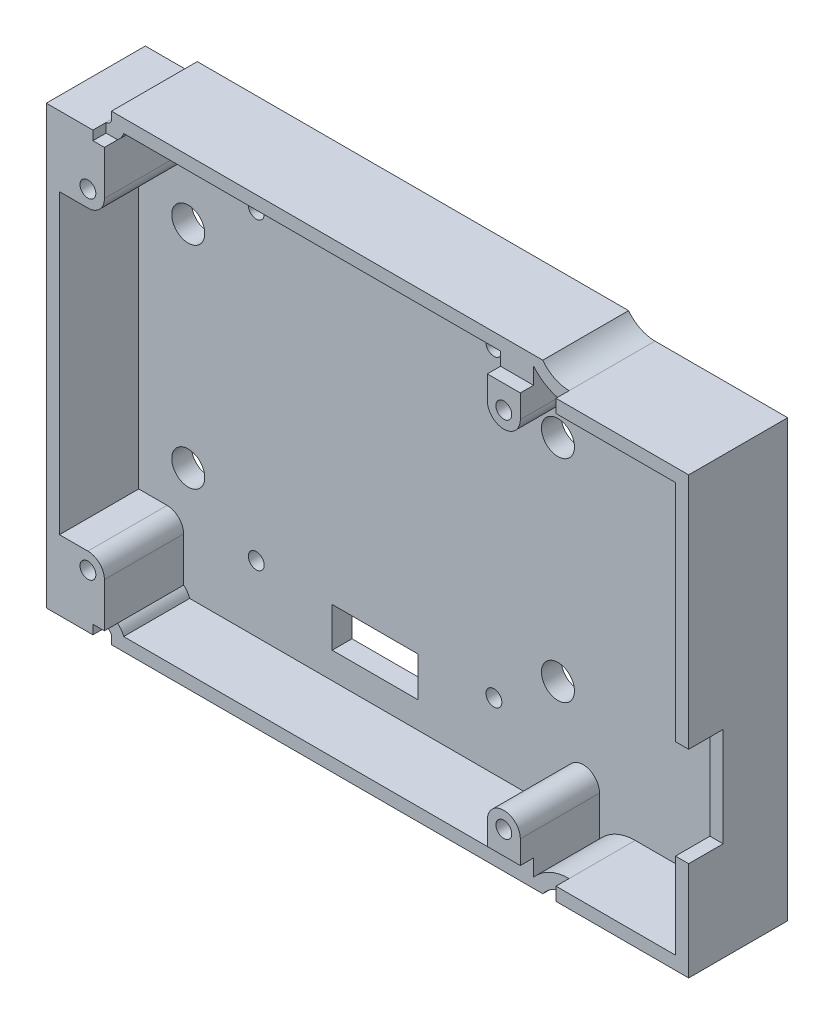
SolidWorks part; units mm, degrees
ref_plane "Ebene vorne" through (0, 0, 0) normal (0, 0, 1) x (1, 0, 0)
ref_plane "Ebene oben" through (0, 0, 0) normal (0, 1, 0) x (1, 0, 0)
ref_plane "Ebene rechts" through (0, 0, 0) normal (1, 0, 0) x (0, 0, -1)
sketch "Skizze1" plane through (0, 0, 0) normal (0, 0, 1) x (1, 0, 0)
  line L0 (-40.78, 38.7) -> (-40.78, 33.92)
  line L1 (-41.59, 33.11) -> (-48.65, 33.11)
  line L2 (-48.65, 33.11) -> (-48.65, -33.11)
  line L3 (-48.65, -33.11) -> (-41.59, -33.11)
  line L4 (-40.78, -33.92) -> (-40.78, -38.7)
  line L5 (-40.78, -38.7) -> (-39.35, -38.7)
  line L6 (-39.35, -38.7) -> (-39.35, 38.7)
  line L7 (-39.35, 38.7) -> (-40.78, 38.7)
  line L8 (48.65, 3) -> (45.65, 3)
  line L9 (45.65, 3) -> (45.65, -30)
  line L10 (45.65, -30) -> (34.2, -30)
  line L11 (34.2, -33) -> (48.65, -33)
  line L12 (48.65, -33) -> (48.65, 3)
  line L13 (45.65, 18) -> (48.65, 18)
  line L14 (48.65, 18) -> (48.65, 33)
  line L15 (48.65, 33) -> (34.2, 33)
  line L16 (34.2, 30) -> (45.65, 30)
  line L17 (45.65, 30) -> (45.65, 18)
  line L18 (34.2, 33) -> (28.5521, 33)
  line L19 (23.85, 36.3) -> (5.65, 36.3)
  line L20 (2.287, 35) -> (-20.522, 35)
  line L21 (-25.35, 38.7) -> (-27.35, 38.7)
  line L22 (-27.35, 38.7) -> (-27.35, -38.7)
  line L23 (-27.35, -38.7) -> (-25.35, -38.7)
  line L24 (-20.522, -35) -> (2.287, -35)
  line L25 (5.65, -36.3) -> (23.85, -36.3)
  line L26 (28.5521, -33) -> (34.2, -33)
  line L27 (34.2, -30) -> (23.85, -30)
  line L28 (23.85, -30) -> (23.85, -24)
  line L29 (23.85, -24) -> (17.45, -24)
  line L30 (17.45, -24) -> (17.45, -33.3)
  line L31 (17.45, -33.3) -> (9.3559, -33.3)
  line L32 (7.65, -33) -> (-24.35, -33)
  line L33 (-24.35, -33) -> (-24.35, 33)
  line L34 (-24.35, 33) -> (7.65, 33)
  line L35 (9.3559, 33.3) -> (17.45, 33.3)
  line L36 (17.45, 33.3) -> (17.45, 24)
  line L37 (17.45, 24) -> (23.85, 24)
  line L38 (23.85, 24) -> (23.85, 30)
  line L39 (23.85, 30) -> (34.2, 30)
  line L40 (-39.35, -38.7) -> (-27.35, -38.7)
  line L41 (-39.35, 38.7) -> (-27.35, 38.7)
  line L42 (48.65, 18) -> (48.65, 3)
  arc A0 (-41.59, 33.11) -> (-40.78, 33.92) centre (-41.59, 33.92) ccw
  arc A1 (-40.78, -33.92) -> (-41.59, -33.11) centre (-41.59, -33.92) ccw
  arc A2 (23.85, 36.3) -> (28.5521, 33) centre (28.5521, 38) ccw
  arc A3 (2.287, 35) -> (5.65, 36.3) centre (2.287, 40) ccw
  arc A4 (-25.35, 38.7) -> (-20.522, 35) centre (-20.522, 40) ccw
  arc A5 (-20.522, -35) -> (-25.35, -38.7) centre (-20.522, -40) ccw
  arc A6 (5.65, -36.3) -> (2.287, -35) centre (2.287, -40) ccw
  arc A7 (28.5521, -33) -> (23.85, -36.3) centre (28.5521, -38) ccw
  arc A8 (7.65, -33) -> (9.3559, -33.3) centre (9.3559, -28.3) ccw
  arc A9 (9.3559, 33.3) -> (7.65, 33) centre (9.3559, 28.3) ccw
extrude "Aufsatz-Linear austragen1" add sketch "Skizze1" along normal blind 15 contours A1 L4 L5 L6 L7 L0 A0 L1 L2 L3 | L41 L6 L40 L22 | A9 L35 L36 L37 L38 L39 L16 L17 L13 L14 L15 L18 A2 L19 A3 L20 A4 L21 L22 L23 A5 L24 A6 L25 A7 L26 L11 L12 L8 L9 L10 L27 L28 L29 L30 L31 A8 L32 L33 L34 | L35 A9 L34 L33 L32 A8 L31 L30 L29 L28 L27 L10 L9 L8 L42 L13 L17 L16 L39 L38 L37 L36 region at (-43.8991, 0, 0) region at (-33.35, 0, 0) region at (-26.35, 37.6153, 0) region at (10.0511, 0.1068, 0)
sketch "Skizze2" plane through (0, 0, 15) normal (0, 0, 1) x (1, 0, 0)
  line L56 (46.65, -31) -> (46.65, 31)
  line L57 (46.65, 31) -> (28.5521, 31)
  line L58 (22.6099, 34.3) -> (6.3502, 34.3)
  line L59 (2.287, 33) -> (-20.522, 33)
  line L60 (-26.6953, 36.7) -> (-38.78, 36.7)
  line L61 (-38.78, 36.7) -> (-38.78, 33.92)
  line L62 (-41.59, 31.11) -> (-46.65, 31.11)
  line L63 (-46.65, 31.11) -> (-46.65, -31.11)
  line L64 (-46.65, -31.11) -> (-41.59, -31.11)
  line L65 (-38.78, -33.92) -> (-38.78, -36.7)
  line L66 (-38.78, -36.7) -> (-26.6953, -36.7)
  line L67 (-20.522, -33) -> (2.287, -33)
  line L68 (6.3502, -34.3) -> (22.6099, -34.3)
  line L69 (28.5521, -31) -> (46.65, -31)
  line L70 (46.65, -31) -> (46.65, 31)
  line L71 (46.65, 31) -> (28.5521, 31)
  line L72 (22.6099, 34.3) -> (6.3502, 34.3)
  line L73 (2.287, 33) -> (-20.522, 33)
  line L74 (-26.6953, 36.7) -> (-38.78, 36.7)
  line L75 (-38.78, 36.7) -> (-38.78, 33.92)
  line L76 (-41.59, 31.11) -> (-46.65, 31.11)
  line L77 (-46.65, 31.11) -> (-46.65, -31.11)
  line L78 (-46.65, -31.11) -> (-41.59, -31.11)
  line L79 (-38.78, -33.92) -> (-38.78, -36.7)
  line L80 (-38.78, -36.7) -> (-26.6953, -36.7)
  line L81 (-20.522, -33) -> (2.287, -33)
  line L82 (6.3502, -34.3) -> (22.6099, -34.3)
  line L83 (28.5521, -31) -> (46.65, -31)
  arc A32 (22.6099, 34.3) -> (28.5521, 31) centre (28.5521, 38) ccw
  arc A33 (2.287, 33) -> (6.3502, 34.3) centre (2.287, 40) ccw
  arc A34 (-26.6953, 36.7) -> (-20.522, 33) centre (-20.522, 40) ccw
  arc A35 (-41.59, 31.11) -> (-38.78, 33.92) centre (-41.59, 33.92) ccw
  arc A36 (-38.78, -33.92) -> (-41.59, -31.11) centre (-41.59, -33.92) ccw
  arc A37 (-20.522, -33) -> (-26.6953, -36.7) centre (-20.522, -40) ccw
  arc A38 (6.3502, -34.3) -> (2.287, -33) centre (2.287, -40) ccw
  arc A39 (28.5521, -31) -> (22.6099, -34.3) centre (28.5521, -38) ccw
  arc A40 (22.6099, 34.3) -> (28.5521, 31) centre (28.5521, 38) ccw
  arc A41 (2.287, 33) -> (6.3502, 34.3) centre (2.287, 40) ccw
  arc A42 (-26.6953, 36.7) -> (-20.522, 33) centre (-20.522, 40) ccw
  arc A43 (-41.59, 31.11) -> (-38.78, 33.92) centre (-41.59, 33.92) ccw
  arc A44 (-38.78, -33.92) -> (-41.59, -31.11) centre (-41.59, -33.92) ccw
  arc A45 (-20.522, -33) -> (-26.6953, -36.7) centre (-20.522, -40) ccw
  arc A46 (6.3502, -34.3) -> (2.287, -33) centre (2.287, -40) ccw
  arc A47 (28.5521, -31) -> (22.6099, -34.3) centre (28.5521, -38) ccw
  dimension "D1" = 2
extrude "Schnitt-Linear austragen1" cut sketch "Skizze2" against normal blind 12
sketch "Skizze3" plane through (0, 0, 3) normal (0, 0, 1) x (1, 0, 0)
  line L1 (-48.65, 0) -> (48.65, 0) construction
  line L2 (48.65, -33) -> (48.65, 33) construction
  line L3 (-48.65, 33.11) -> (-48.65, -33.11) construction
  circle A0 centre (20.65, 27.5) radius 1.2
  circle A2 centre (-42.35, 25) radius 1.2
  circle A3 centre (-42.35, -25) radius 1.2
  circle A4 centre (20.65, -27.5) radius 1.2
  dimension "D1" = 2.4
extrude "Schnitt-Linear austragen2" cut sketch "Skizze3" against normal blind 10
sketch "Skizze4" plane through (48.65, 0, 0) normal (1, 0, 0) x (0, 0, -1)
  line L0 (-15, -33) -> (-15, 33) construction
  line L1 (-15, -3) -> (-9.78, -3)
  line L2 (-15, -3) -> (-15, -18.0065)
  line L3 (-15, -18.0065) -> (-9.78, -18.0065)
  line L4 (-9.78, -3) -> (-9.78, -18.0065)
  line L5 (-15, -3) -> (-20.215, -3) construction
  dimension "D1" = 5.22
extrude "Schnitt-Linear austragen3" cut sketch "Skizze4" against normal blind 5
sketch "Skizze5" plane through (0, 0, 0) normal (0, 0, -1) x (-1, 0, 0)
  line L0 (-20.65, 27.5) -> (-20.65, -27.5) construction
  line L1 (42.35, 25) -> (42.35, -25) construction
  line L2 (-20.65, 0) -> (42.35, 0) construction
  line L3 (10.85, 0) -> (10.85, -35) construction
  line L4 (20.522, -35) -> (-2.287, -35) construction
  circle A0 centre (-7.15, -23) radius 1.2
  circle A1 centre (28.85, -23) radius 1.2
  circle A2 centre (28.85, 23) radius 1.2
  circle A3 centre (-7.15, 23) radius 1.2
  dimension "D3" = 2.4
  dimension "D1" = 18
  dimension "D2" = 12
extrude "Schnitt-Linear austragen4" cut sketch "Skizze5" against normal through all both
sketch "Skizze6" plane through (0, 0, 0) normal (0, 0, -1) x (-1, 0, 0)
  line L0 (11.15, -17.75) -> (11.15, 17.75) construction
  line L1 (-21.35, -17.75) -> (43.65, -17.75) construction
  line L2 (43.65, 17.75) -> (-21.35, 17.75) construction
  line L3 (48.65, 0) -> (-26.35, 0) construction
  line L4 (48.65, 33.11) -> (48.65, -33.11) construction
  line L5 (-26.35, -10) -> (-26.35, 10) construction
  circle A0 centre (-16.85, -16) radius 2.5
  circle A1 centre (-16.85, 16) radius 2.5
  circle A2 centre (39.15, 16) radius 2.5
  circle A3 centre (39.15, -16) radius 2.5
  dimension "D1" = 5
  dimension "D2" = 28
  dimension "D3" = 16
extrude "Schnitt-Linear austragen5" cut sketch "Skizze6" against normal through all both
sketch "Skizze7" plane through (0, 0, 0) normal (0, 0, -1) x (-1, 0, 0)
  line L1 (17.35, -29) -> (4.35, -29)
  line L2 (17.35, -29) -> (17.35, -23)
  line L3 (17.35, -23) -> (4.35, -23)
  line L4 (4.35, -29) -> (4.35, -23)
  line L5 (17.35, 23) -> (4.35, 23)
  line L6 (17.35, 23) -> (17.35, 29)
  line L7 (17.35, 29) -> (4.35, 29)
  line L8 (4.35, 23) -> (4.35, 29)
extrude "Schnitt-Linear austragen6" cut sketch "Skizze7" against normal through all both
sketch "Skizze8" plane through (0, 0, 3) normal (0, 0, 1) x (1, 0, 0)
  line L0 (-48.65, 0) -> (48.65, 0) construction
  line L1 (-48.65, 33.11) -> (-48.65, -33.11) construction
  line L2 (48.65, -3) -> (48.65, 33) construction
  line L3 (0, 0) -> (0, 35) construction
  line L4 (2.287, 35) -> (-20.522, 35) construction
  circle A0 centre (20.65, 27.5) radius 2.5
  circle A1 centre (20.65, 27.5) radius 1.2
  circle A2 centre (20.65, -27.5) radius 1.2
  circle A3 centre (20.65, -27.5) radius 2.5
  circle A4 centre (-42.35, 25) radius 2.5
  circle A5 centre (-42.35, 25) radius 1.2
  circle A6 centre (-42.35, -25) radius 1.2
  circle A7 centre (-42.35, -25) radius 2.5
  dimension "D1" = 5
  dimension "D2" = 5
extrude "Aufsatz-Linear austragen2" add sketch "Skizze8" along normal up to surface (12 mm away) up to face at (-5.0444, -0.8753, 15)
sketch "Skizze9" plane through (0, 0, 3) normal (0, 0, 1) x (1, 0, 0)
  line L0 (-39.85, 25) -> (-39.85, 31.933)
  line L1 (-39.85, 31.933) -> (-46.65, 31.933)
  line L2 (-46.65, 31.933) -> (-46.65, 22.5)
  line L3 (-46.65, 31.11) -> (-46.65, -31.11) construction
  line L4 (-46.65, 22.5) -> (-42.35, 22.5)
  line L5 (-48.65, 0) -> (46.65, 0) construction
  line L6 (-48.65, 33.11) -> (-48.65, -33.11) construction
  line L7 (46.65, -31) -> (46.65, 31) construction
  line L8 (18.15, 27.5) -> (18.15, 33)
  line L10 (23.15, 27.5) -> (23.15, 34.3)
  line L17 (-46.65, -22.5) -> (-42.35, -22.5)
  line L18 (-46.65, -31.933) -> (-46.65, -22.5)
  line L19 (-39.85, -31.933) -> (-46.65, -31.933)
  line L20 (-39.85, -25) -> (-39.85, -31.933)
  line L21 (-20.522, -33) -> (-38.9349, -33)
  line L22 (-20.522, -35) -> (-38.78, -35)
  line L23 (-38.78, -33.92) -> (-38.78, -36.7) construction
  line L24 (-38.78, -35) -> (-38.9349, -33)
  line L25 (-20.522, -33) -> (-20.522, -35)
  line L26 (-20.522, 33) -> (-20.522, 35)
  line L27 (-38.78, 35) -> (-38.9349, 33)
  line L28 (-20.522, 35) -> (-38.78, 35)
  line L29 (-20.522, 33) -> (-38.9349, 33)
  line L30 (2.287, 33) -> (18.15, 33)
  line L31 (2.287, 35) -> (24.5521, 35)
  line L32 (24.5521, 35) -> (24.5521, 34.3)
  line L33 (23.15, 34.3) -> (24.5521, 34.3)
  line L34 (2.287, 35) -> (2.287, 33)
  line L35 (2.287, -35) -> (2.287, -33)
  line L36 (23.15, -34.3) -> (24.5521, -34.3)
  line L37 (24.5521, -35) -> (24.5521, -34.3)
  line L38 (2.287, -35) -> (24.5521, -35)
  line L39 (2.287, -33) -> (18.15, -33)
  line L40 (23.15, -27.5) -> (23.15, -34.3)
  line L41 (18.15, -27.5) -> (18.15, -33)
  circle A0 centre (-42.35, 25) radius 2.5 construction
  circle A1 centre (-42.35, 25) radius 2.5 construction
  arc A2 (-39.85, 25) -> (-42.35, 22.5) centre (-42.35, 25) cw
  circle A3 centre (-42.35, 25) radius 1.2
  circle A4 centre (20.65, 27.5) radius 2.5 construction
  circle A5 centre (20.65, 27.5) radius 2.5 construction
  arc A7 (23.15, 27.5) -> (18.15, 27.5) centre (20.65, 27.5) cw
  circle A8 centre (20.65, 27.5) radius 1.2
  circle A11 centre (-42.35, -25) radius 1.2
  arc A12 (-39.85, -25) -> (-42.35, -22.5) centre (-42.35, -25) ccw
  arc A13 (-38.78, -33.92) -> (-41.59, -31.11) centre (-41.59, -33.92) ccw construction
  arc A14 (23.85, 36.3) -> (28.5521, 33) centre (28.5521, 38) ccw construction
  circle A15 centre (20.65, -27.5) radius 1.2
  arc A16 (23.15, -27.5) -> (18.15, -27.5) centre (20.65, -27.5) ccw
extrude "Aufsatz-Linear austragen3" add sketch "Skizze9" along normal up to surface (12 mm away) up to face at (-5.0444, -0.8753, 15)
sketch "Skizze10" plane through (0, 0, 15) normal (0, 0, 1) x (1, 0, 0)
  line L0 (-40.78, 38.7) -> (-40.78, 33.92) construction
  line L1 (-40.78, 35) -> (36.193, 35)
  line L2 (-40.78, 35) -> (-40.78, 40.1609)
  line L3 (-40.78, 40.1609) -> (36.193, 40.1609)
  line L4 (36.193, 35) -> (36.193, 40.1609)
  line L5 (-48.65, 0) -> (46.65, 0) construction
  line L6 (-48.65, 33.11) -> (-48.65, -33.11) construction
  line L7 (46.65, -31) -> (46.65, 31) construction
  line L8 (36.193, -35) -> (36.193, -40.1609)
  line L9 (-40.78, -40.1609) -> (36.193, -40.1609)
  line L10 (-40.78, -35) -> (-40.78, -40.1609)
  line L11 (-40.78, -35) -> (36.193, -35)
extrude "Schnitt-Linear austragen7" cut sketch "Skizze10" against normal through all both and the other way through all
sketch "Skizze11" plane through (0, 0, 15) normal (0, 0, 1) x (1, 0, 0)
  line L19 (-48.65, 0) -> (0, 0) construction
  line L20 (-48.65, 33.11) -> (-48.65, -33.11) construction
  line L33 (-41.59, 31.7135) -> (-41.59, 35)
  line L34 (-41.59, 35) -> (28.5521, 35)
  line L35 (28.5521, 35) -> (28.5521, 31)
  line L36 (28.5521, 31) -> (18.15, 31)
  line L37 (18.15, 33) -> (18.15, 27.5) construction
  line L38 (18.15, 31) -> (18.15, 33)
  line L39 (18.15, 33) -> (-38.9349, 33)
  line L40 (-38.9349, 33) -> (-38.9349, 31.7135)
  line L41 (-38.9349, 31.7135) -> (-41.59, 31.7135)
  line L42 (-38.9349, -33) -> (-38.9349, -31.7135)
  line L43 (18.15, -33) -> (-38.9349, -33)
  line L44 (18.15, -31) -> (18.15, -33)
  line L45 (28.5521, -31) -> (18.15, -31)
  line L46 (28.5521, -35) -> (28.5521, -31)
  line L47 (-41.59, -35) -> (28.5521, -35)
  line L48 (-41.59, -31.7135) -> (-41.59, -35)
  line L49 (-38.9349, -31.7135) -> (-41.59, -31.7135)
extrude "Schnitt-Linear austragen8" cut sketch "Skizze11" against normal blind 2
